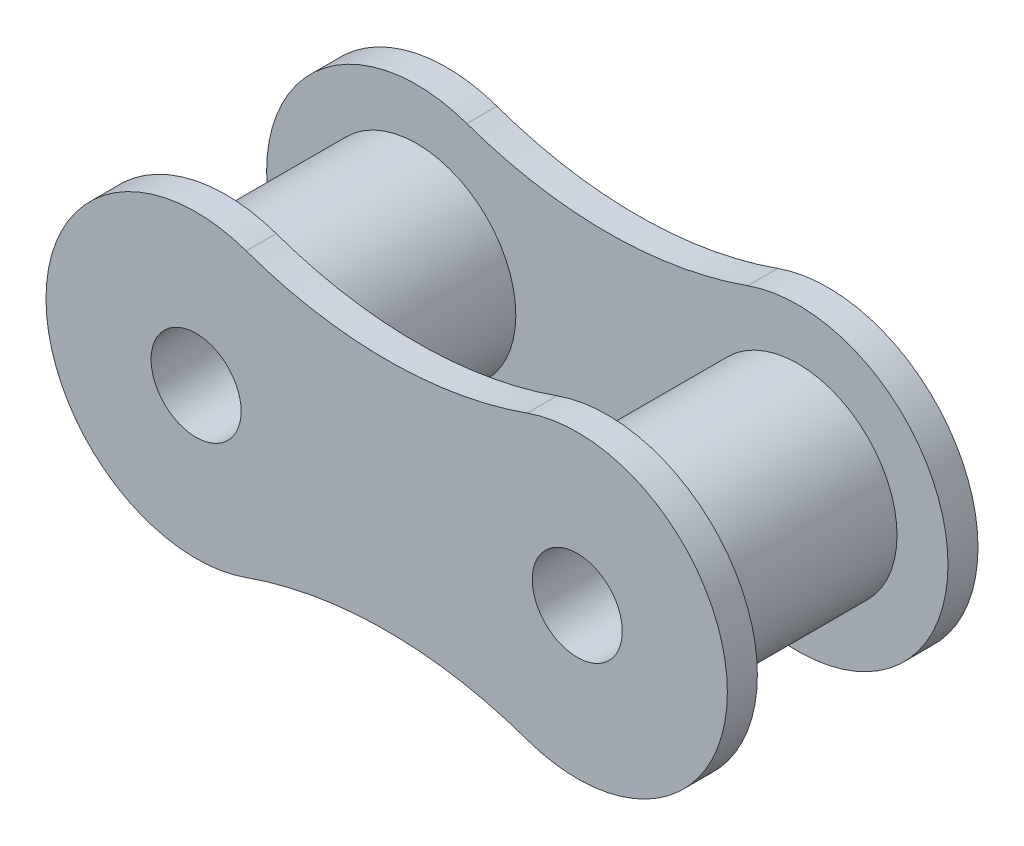
SolidWorks part; units mm, degrees
material "AISI 304"
ref_plane "Plane1" through (0, 0, 0) normal (0, 0, 1) x (1, 0, 0)
ref_plane "Plane2" through (0, 0, 0) normal (0, 1, 0) x (1, 0, 0)
ref_plane "Plane3" through (0, 0, 0) normal (1, 0, 0) x (0, 0, -1)
sketch "Sketch1" plane through (0, 0, 0) normal (0, 0, 1) x (1, 0, 0)
  line L0 (3.175, 2.6926) -> (3.175, -2.6926) construction
  arc A0 (0.8355, 2.3562) -> (0.8355, -2.3562) centre (0, 0) ccw
  circle A4 centre (0, 0) radius 0.75
  arc A8 (5.5145, 2.3562) -> (5.5145, -2.3562) centre (6.35, 0) cw
  circle A9 centre (6.35, 0) radius 0.75
  arc A10 (0.8355, -2.3562) -> (5.5145, -2.3562) centre (3.175, -8.9537) cw
  arc A11 (0.8355, 2.3562) -> (5.5145, 2.3562) centre (3.175, 8.9537) ccw
  dimension "D1" = 5
  dimension "D2" = 3.175
  dimension "D6" = 1.5
  dimension "D3" = 7
extrude "Boss-Extrude1" add sketch "Sketch1" along normal blind 0.5
sketch "Sketch2" plane through (0, 0, 0.5) normal (0, 0, 1) x (1, 0, 0)
  circle A0 centre (0, 0) radius 1.651
  circle A2 centre (6.35, 0) radius 1.651
  circle M2 centre (0, 0) radius 0.75
  circle M7 centre (6.35, 0) radius 0.75
  dimension "D1" = 3.302
  dimension "D2" = 3.302
extrude "Boss-Extrude2" add sketch "Sketch2" along normal blind 3.175 contours A2 M7 | A0 M2 region at (-1.6043, 0, 0.5) region at (4.7457, 0, 0.5)
ref_plane "Plane4" through (0, 0, 2.0875) normal (0, 0, 1) x (1, 0, 0)
mirror "Mirror1" about plane through (0, 0, 2.0875) normal (0, 0, 1) of bodies 105 104
